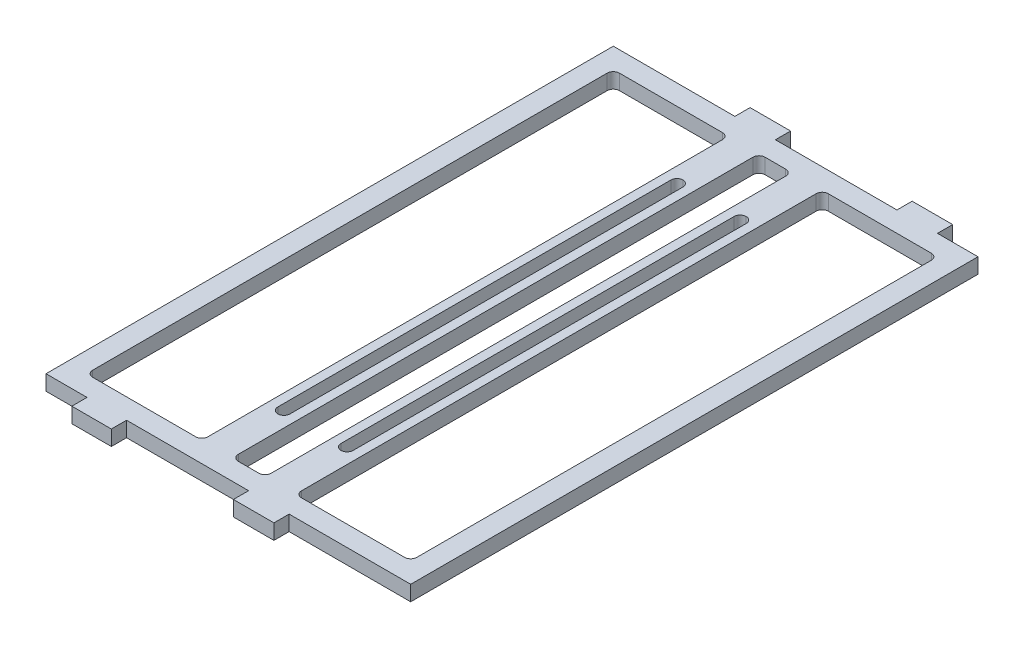
SolidWorks part; units mm, degrees
material "6061-T6 (SS)"
ref_plane "Front Plane" through (0, 0, 0) normal (0, 0, 1) x (1, 0, 0)
ref_plane "Top Plane" through (0, 0, 0) normal (0, 1, 0) x (1, 0, 0)
ref_plane "Right Plane" through (0, 0, 0) normal (1, 0, 0) x (0, 0, -1)
sketch "Sketch1" plane through (0, 0, 0) normal (0, 1, 0) x (1, 0, 0)
  line L0 (50.8, 82.55) -> (-50.8, 82.55)
  line L1 (57.15, 88.9) -> (-57.15, 88.9)
  line L2 (57.15, 88.9) -> (57.15, -88.9)
  line L3 (57.15, -88.9) -> (-57.15, -88.9)
  line L4 (-57.15, 88.9) -> (-57.15, -88.9)
  line L5 (57.15, 88.9) -> (-57.15, -88.9) construction
  line L6 (57.15, -88.9) -> (-57.15, 88.9) construction
  line L7 (-50.8, 82.55) -> (-50.8, -82.55)
  line L8 (50.8, -82.55) -> (-50.8, -82.55)
  line L9 (50.8, 82.55) -> (50.8, -82.55)
  point P0 (0, 0)
  dimension "D1" = 114.3
  dimension "D2" = 177.8
  dimension "D3" = 6.35
extrude "Boss-Extrude1" add sketch "Sketch1" along normal blind 4.7625
sketch "Sketch2" plane through (0, 0, 88.9) normal (0, 0, 1) x (1, 0, 0)
  line L0 (-57.15, 2.3813) -> (57.15, 2.3813) construction
  line L1 (-57.15, 4.7625) -> (-57.15, 0) construction
  line L2 (57.15, 4.7625) -> (57.15, 0) construction
  line L3 (-57.15, 0) -> (57.15, 0) construction
  line L4 (-31.9066, 4.7625) -> (-44.2934, 4.7625)
  line L5 (-31.9066, 4.7625) -> (-31.9066, 0)
  line L6 (-31.9066, 0) -> (-44.2934, 0)
  line L7 (-44.2934, 4.7625) -> (-44.2934, 0)
  line L8 (-31.9066, 4.7625) -> (-44.2934, 0) construction
  line L9 (-31.9066, 0) -> (-44.2934, 4.7625) construction
  line L11 (19.05, 4.7625) -> (6.35, 4.7625)
  line L12 (19.05, 4.7625) -> (19.05, 0)
  line L13 (19.05, 0) -> (6.35, 0)
  line L14 (6.35, 4.7625) -> (6.35, 0)
  line L15 (19.05, 4.7625) -> (6.35, 0) construction
  line L16 (19.05, 0) -> (6.35, 4.7625) construction
  point P6 (-38.1, 2.3813)
  point P13 (12.7, 2.3813)
  dimension "D1" = 19.05
  dimension "D2" = 50.8
  dimension "D3" = 12.7
extrude "Boss-Extrude2" add sketch "Sketch2" along normal blind 4.7625
sketch "Sketch3" plane through (0, 0, -88.9) normal (0, 0, -1) x (-1, 0, 0)
  line L0 (-57.15, 2.3813) -> (57.15, 2.3813) construction
  line L1 (-57.15, 4.7625) -> (-57.15, 0) construction
  line L2 (57.15, 4.7625) -> (57.15, 0) construction
  line L3 (-57.15, 0) -> (57.15, 0) construction
  line L4 (-31.75, 4.7625) -> (-44.45, 4.7625)
  line L5 (-31.75, 4.7625) -> (-31.75, 0)
  line L6 (-31.75, 0) -> (-44.45, 0)
  line L7 (-44.45, 4.7625) -> (-44.45, 0)
  line L8 (-31.75, 4.7625) -> (-44.45, 0) construction
  line L9 (-31.75, 0) -> (-44.45, 4.7625) construction
  line L11 (19.05, 4.7625) -> (6.35, 4.7625)
  line L12 (19.05, 4.7625) -> (19.05, 0)
  line L13 (19.05, 0) -> (6.35, 0)
  line L14 (6.35, 4.7625) -> (6.35, 0)
  line L15 (19.05, 4.7625) -> (6.35, 0) construction
  line L16 (19.05, 0) -> (6.35, 4.7625) construction
  point P6 (-38.1, 2.3812)
  point P13 (12.7, 2.3812)
  dimension "D1" = 12.7
  dimension "D2" = 12.7
  dimension "D3" = 19.05
  dimension "D4" = 50.8
extrude "Boss-Extrude3" add sketch "Sketch3" along normal blind 4.7625
sketch "Sketch4" plane through (0, 4.7625, 0) normal (0, 1, 0) x (-1, 0, 0)
  line L0 (57.15, 0) -> (-57.15, 0) construction
  line L1 (57.15, -88.9) -> (57.15, 88.9) construction
  line L2 (-57.15, 88.9) -> (-57.15, -88.9) construction
  line L3 (57.15, 88.9) -> (44.2934, 88.9) construction
  line L4 (5.1435, -88.9) -> (14.6685, -88.9)
  line L5 (5.1435, -88.9) -> (5.1435, 88.9)
  line L6 (5.1435, 88.9) -> (14.6685, 88.9)
  line L7 (14.6685, -88.9) -> (14.6685, 88.9)
  line L8 (5.1435, -88.9) -> (14.6685, 88.9) construction
  line L9 (5.1435, 88.9) -> (14.6685, -88.9) construction
  line L10 (-19.05, 88.9) -> (-57.15, 88.9) construction
  line L11 (-14.6685, -88.9) -> (-5.1435, -88.9)
  line L12 (-14.6685, -88.9) -> (-14.6685, 88.9)
  line L13 (-14.6685, 88.9) -> (-5.1435, 88.9)
  line L14 (-5.1435, -88.9) -> (-5.1435, 88.9)
  line L15 (-14.6685, -88.9) -> (-5.1435, 88.9) construction
  line L16 (-14.6685, 88.9) -> (-5.1435, -88.9) construction
  line L18 (8.001, -63.5) -> (11.811, -63.5)
  line L19 (8.001, -63.5) -> (8.001, 63.5)
  line L20 (8.001, 63.5) -> (11.811, 63.5)
  line L21 (11.811, -63.5) -> (11.811, 63.5)
  line L22 (8.001, -63.5) -> (11.811, 63.5) construction
  line L23 (8.001, 63.5) -> (11.811, -63.5) construction
  line L24 (-11.811, -63.5) -> (-8.001, -63.5)
  line L25 (-11.811, -63.5) -> (-11.811, 63.5)
  line L26 (-11.811, 63.5) -> (-8.001, 63.5)
  line L27 (-8.001, -63.5) -> (-8.001, 63.5)
  line L28 (-11.811, -63.5) -> (-8.001, 63.5) construction
  line L29 (-11.811, 63.5) -> (-8.001, -63.5) construction
  point P6 (9.906, 0)
  point P13 (-9.906, 0)
  point P20 (9.906, 0)
  point P26 (-9.906, 0)
  dimension "D1" = 9.525
  dimension "D2" = 9.525
  dimension "D3" = 9.906
  dimension "D4" = 9.906
  dimension "D5" = 127
  dimension "D6" = 3.81
  dimension "D7" = 127
  dimension "D8" = 3.81
extrude "Boss-Extrude4" add sketch "Sketch4" against normal blind 4.7625
fillet "Fillet1" radius 1.905 20 edges at (-8.001, 2.3813, -63.5) (-11.811, 2.3813, -63.5) (8.001, 2.3813, -63.5) (11.811, 2.3813, -63.5) (-8.001, 2.3813, 63.5) (-11.811, 2.3813, 63.5) (8.001, 2.3813, 63.5) (11.811, 2.3813, 63.5) (-5.1435, 2.3813, 82.55) (5.1435, 2.3813, 82.55) (-5.1435, 2.3813, -82.55) (5.1435, 2.3813, -82.55) (-14.6685, 2.3813, -82.55) (-50.8, 2.3813, -82.55) (-50.8, 2.3813, 82.55) (-14.6685, 2.3813, 82.55) (14.6685, 2.3813, 82.55) (50.8, 2.3813, 82.55) (14.6685, 2.3813, -82.55) (50.8, 2.3813, -82.55)
